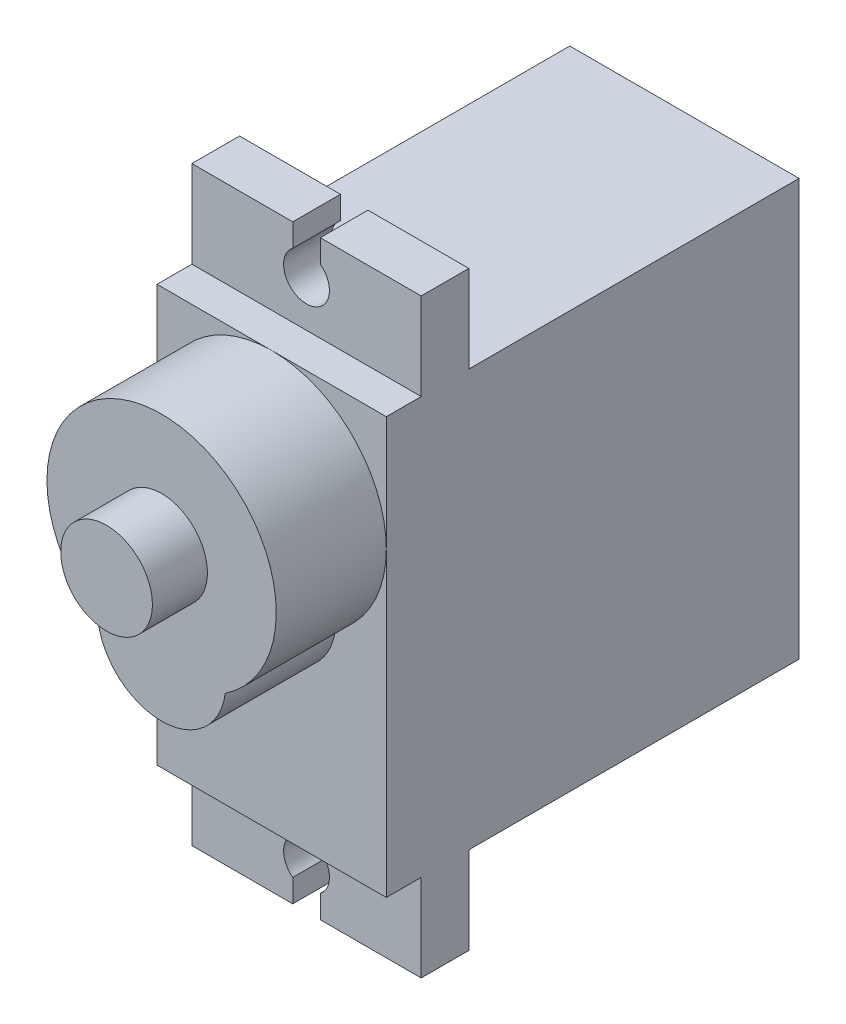
SolidWorks part; units mm, degrees
ref_plane "Front Plane" through (0, 0, 0) normal (1, 0, 0) x (0, 1, 0)
ref_plane "Top Plane" through (0, 0, 0) normal (0, 0, 1) x (0, 1, 0)
ref_plane "Right Plane" through (0, 0, 0) normal (0, 1, 0) x (-1, 0, 0)
sketch "Sketch2" plane through (0, 0, 0) normal (1, 0, 0) x (0, 1, 0)
  line L0 (0, 0) -> (0, 18)
  line L1 (0, 18) -> (-4.75, 18)
  line L2 (-4.75, 18) -> (-4.75, 20.6)
  line L3 (-4.75, 20.6) -> (0, 20.6)
  line L4 (0, 20.6) -> (0, 22.5)
  line L5 (0, 22.5) -> (22.7, 22.5)
  line L6 (22.7, 22.5) -> (22.7, 20.6)
  line L7 (22.7, 20.6) -> (27.45, 20.6)
  line L8 (27.45, 20.6) -> (27.45, 18)
  line L9 (27.45, 18) -> (22.7, 18)
  line L10 (22.7, 18) -> (22.7, 0)
  line L11 (22.7, 0) -> (0, 0)
  dimension "D1" = 18
  dimension "D2" = 22.5
  dimension "D3" = 2.6
  dimension "D4" = 32.2
  dimension "D5" = 2.6
  dimension "D6" = 22.7
extrude "Boss-Extrude1" add sketch "Sketch2" along normal blind 12.5
sketch "Sketch3" plane through (0, 0, 22.5) normal (0, 0, 1) x (1, 0, 0)
  line L0 (6.25, -23.4562) -> (6.25, 23.4562) construction
  line L2 (12.5, 0) -> (0, 0) construction
  line L3 (12.5, 22.7) -> (12.5, 0) construction
  line L4 (0, 22.7) -> (0, 0) construction
  line L5 (12.5, 22.7) -> (0, 22.7) construction
  circle A0 centre (6.25, 16.45) radius 6.25
  circle A1 centre (6.25, 11.7) radius 3.5
  point P4 (6.25, 8.2)
  point P7 (6.25, 0)
  point P13 (6.25, 22.7)
  dimension "D1" = 14.5
  dimension "D2" = 7
extrude "Boss-Extrude2" add sketch "Sketch3" along normal blind 6 contours A1 L0 A0 | L0 A1 A0 | A0 L0 A1 | L0 A0 A1 | A1 L0 A0 | L0 A1 A0 region at (4.7627, 9.5885, 22.5) region at (7.7373, 9.5885, 22.5) region at (4.7653, 12.5623, 22.5) region at (7.7347, 12.5623, 22.5) region at (3.2629, 17.5637, 22.5) region at (9.2371, 17.5637, 22.5)
sketch "Sketch4" plane through (0, 0, 28.5) normal (0, 0, 1) x (1, 0, 0)
  circle A0 centre (6.25, 16.45) radius 2.5
  arc A1 (9.7213, 11.2526) -> (2.7787, 11.2526) centre (6.25, 16.45) ccw construction
  dimension "D1" = 5
extrude "Boss-Extrude3" add sketch "Sketch4" along normal blind 3
sketch "Sketch5" plane through (0, 0, 20.6) normal (0, 0, 1) x (1, 0, 0)
  line L0 (5.5, 27.45) -> (5.5, 26.2)
  line L1 (12.5, 27.45) -> (0, 27.45) construction
  line L2 (7, 26.2) -> (7, 27.45)
  line L3 (5.5, -3.5) -> (5.5, -4.75)
  line L4 (12.5, -4.75) -> (0, -4.75) construction
  line L5 (7, -3.5) -> (7, -4.75)
  line L6 (5.5, -4.75) -> (7, -4.75)
  line L7 (5.5, 27.45) -> (7, 27.45)
  line L8 (0, 27.45) -> (0, 22.7) construction
  circle A0 centre (6.25, 25.2) radius 1.25
  circle A1 centre (6.25, -2.5) radius 1.25
  point P9 (6.25, 27.45)
  line M7 (12.5, 27.45) -> (0, 27.45)
  dimension "D1" = 27.7
  dimension "D2" = 1.5
  dimension "D3" = 2.5
  dimension "D4" = 2.25
  dimension "D5" = 6.25
extrude "Cut-Extrude1" cut sketch "Sketch5" against normal up to surface (2.6 mm away) contours A0 L2 L0 M7 | A0 | A1 L3 L6 L5 | A1 region at (6.25, 26.9077, 20.6) region at (6.25, 25.2, 20.6) region at (6.25, -4.2077, 20.6) region at (6.25, -2.5, 20.6) up to face at (6.25, 25.075, 18)
